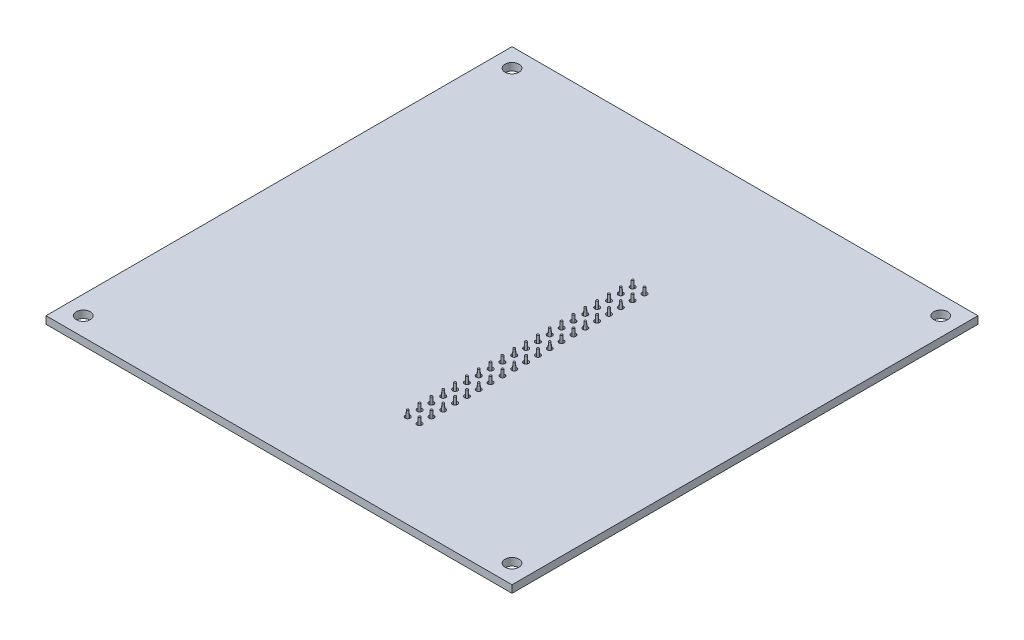
SolidWorks part; units mm, degrees
ref_plane "Front Plane" through (0, 0, 0) normal (0, 0, 1) x (1, 0, 0)
ref_plane "Top Plane" through (0, 0, 0) normal (0, 1, 0) x (1, 0, 0)
ref_plane "Right Plane" through (0, 0, 0) normal (1, 0, 0) x (0, 0, -1)
sketch "Sketch1" plane through (0, 0, 0) normal (0, 1, 0) x (1, 0, 0)
  line L1 (-50, -50) -> (50, -50)
  line L2 (-50, -50) -> (-50, 50)
  line L3 (-50, 50) -> (50, 50)
  line L4 (50, -50) -> (50, 50)
  line L5 (-50, -50) -> (50, 50) construction
  line L6 (-50, 50) -> (50, -50) construction
  point P0 (0, 0)
  dimension "D1" = 100
  dimension "D2" = 100
extrude "Boss-Extrude1" add sketch "Sketch1" along normal blind 1.6
sketch "Sketch2" plane through (0, 1.6, 0) normal (0, 1, 0) x (1, 0, 0)
  line L0 (10.138, -29.974) -> (10.138, -27.434) construction
  circle A0 centre (10.138, -29.974) radius 0.535
  circle A1 centre (7.598, -29.974) radius 0.535
  circle A2 centre (7.598, -27.434) radius 0.535
  circle A3 centre (7.598, -24.894) radius 0.535
  circle A4 centre (7.598, -22.354) radius 0.535
  circle A5 centre (7.598, -19.814) radius 0.535
  circle A6 centre (7.598, -17.274) radius 0.535
  circle A7 centre (7.598, -14.734) radius 0.535
  circle A8 centre (7.598, -12.194) radius 0.535
  circle A9 centre (7.598, -9.654) radius 0.535
  circle A10 centre (7.598, -7.114) radius 0.535
  circle A11 centre (7.598, -4.574) radius 0.535
  circle A12 centre (7.598, -2.034) radius 0.535
  circle A13 centre (7.598, 0.506) radius 0.535
  circle A14 centre (7.598, 3.046) radius 0.535
  circle A15 centre (7.598, 5.586) radius 0.535
  circle A16 centre (7.598, 8.126) radius 0.535
  circle A17 centre (7.598, 10.666) radius 0.535
  circle A18 centre (7.598, 13.206) radius 0.535
  circle A19 centre (7.598, 15.746) radius 0.535
  circle A20 centre (7.598, 18.286) radius 0.535
  circle A21 centre (10.138, -27.434) radius 0.535
  circle A22 centre (10.138, -24.894) radius 0.535
  circle A23 centre (10.138, -22.354) radius 0.535
  circle A24 centre (10.138, -19.814) radius 0.535
  circle A25 centre (10.138, -17.274) radius 0.535
  circle A26 centre (10.138, -14.734) radius 0.535
  circle A27 centre (10.138, -12.194) radius 0.535
  circle A28 centre (10.138, -9.654) radius 0.535
  circle A29 centre (10.138, -7.114) radius 0.535
  circle A30 centre (10.138, -4.574) radius 0.535
  circle A31 centre (10.138, -2.034) radius 0.535
  circle A32 centre (10.138, 0.506) radius 0.535
  circle A33 centre (10.138, 3.046) radius 0.535
  circle A34 centre (10.138, 5.586) radius 0.535
  circle A35 centre (10.138, 8.126) radius 0.535
  circle A36 centre (10.138, 10.666) radius 0.535
  circle A37 centre (10.138, 13.206) radius 0.535
  circle A38 centre (10.138, 15.746) radius 0.535
  circle A39 centre (10.138, 18.286) radius 0.535
  dimension "D1" = 1.07
  dimension "D2" = 39.862
  dimension "D3" = 20.026
  dimension "D6" = 2.54
  dimension "D4" = 2
  dimension "D5" = 20
extrude "Cut-Extrude1" cut sketch "Sketch2" against normal through all
ref_plane "Plane1" through (0, -9.4, 0) normal (0, -1, 0) x (-1, 0, 0)
sketch "Sketch4" plane through (0, -9.4, 0) normal (0, 1, 0) x (1, 0, 0)
  line L0 (9.368, -29.204) -> (10.908, -29.204)
  line L1 (8.868, -31.244) -> (11.408, -31.244)
  line L2 (8.868, -31.244) -> (8.868, -28.704)
  line L3 (8.868, -28.704) -> (11.408, -28.704)
  line L4 (11.408, -31.244) -> (11.408, -28.704)
  line L5 (8.868, -31.244) -> (11.408, -28.704) construction
  line L6 (8.868, -28.704) -> (11.408, -31.244) construction
  line L7 (10.908, -30.744) -> (10.908, -29.204)
  line L8 (9.368, -30.744) -> (10.908, -30.744)
  line L9 (9.368, -30.744) -> (9.368, -29.204)
  point P0 (10.138, -29.974)
  dimension "D1" = 2.54
  dimension "D2" = 2.54
  dimension "D3" = 0.5
extrude "Boss-Extrude2" add sketch "Sketch4" against normal blind 8.4
pattern_linear "LPattern2" count 20 spacing 2.54 along (0, 0, -1) count 2 spacing 2.54 along (-1, 0, 0) of "Boss-Extrude2"
sketch "Sketch5" plane through (0, -9.4, 0) normal (0, -1, 0) x (-1, 0, 0)
  circle A0 centre (-7.598, 3.046) radius 0.535 construction
  circle A1 centre (-7.598, 5.586) radius 0.535 construction
  circle A2 centre (-7.598, 8.126) radius 0.535 construction
  circle A3 centre (-7.598, 10.666) radius 0.535 construction
  circle A4 centre (-7.598, 13.206) radius 0.535 construction
  circle A5 centre (-7.598, 15.746) radius 0.535 construction
  circle A6 centre (-7.598, 18.286) radius 0.535 construction
  circle A7 centre (-10.138, 18.286) radius 0.535 construction
  circle A8 centre (-10.138, 15.746) radius 0.535 construction
  circle A9 centre (-10.138, 13.206) radius 0.535 construction
  circle A10 centre (-10.138, 10.666) radius 0.535 construction
  circle A11 centre (-10.138, 8.126) radius 0.535 construction
  circle A12 centre (-10.138, 5.586) radius 0.535 construction
  circle A13 centre (-10.138, 3.046) radius 0.535 construction
  circle A14 centre (-7.598, 0.506) radius 0.535 construction
  circle A15 centre (-10.138, 0.506) radius 0.535 construction
  circle A16 centre (-10.138, -2.034) radius 0.535 construction
  circle A17 centre (-7.598, -2.034) radius 0.535 construction
  circle A18 centre (-7.598, -4.574) radius 0.535 construction
  circle A19 centre (-10.138, -4.574) radius 0.535 construction
  circle A20 centre (-10.138, -7.114) radius 0.535 construction
  circle A21 centre (-7.598, -7.114) radius 0.535 construction
  circle A22 centre (-7.598, -9.654) radius 0.535 construction
  circle A23 centre (-10.138, -9.654) radius 0.535 construction
  circle A24 centre (-7.598, -12.194) radius 0.535 construction
  circle A25 centre (-10.138, -12.194) radius 0.535 construction
  circle A26 centre (-10.138, -14.734) radius 0.535 construction
  circle A27 centre (-7.598, -14.734) radius 0.535 construction
  circle A28 centre (-7.598, -17.274) radius 0.535 construction
  circle A29 centre (-10.138, -17.274) radius 0.535 construction
  circle A30 centre (-10.138, -19.814) radius 0.535 construction
  circle A31 centre (-7.598, -19.814) radius 0.535 construction
  circle A32 centre (-7.598, -22.354) radius 0.535 construction
  circle A33 centre (-10.138, -22.354) radius 0.535 construction
  circle A34 centre (-7.598, -24.894) radius 0.535 construction
  circle A35 centre (-10.138, -24.894) radius 0.535 construction
  circle A36 centre (-7.598, -27.434) radius 0.535 construction
  circle A37 centre (-10.138, -27.434) radius 0.535 construction
  circle A38 centre (-10.138, -29.974) radius 0.535 construction
  circle A39 centre (-7.598, -29.974) radius 0.535 construction
  circle A40 centre (-7.598, 3.046) radius 0.535
  circle A41 centre (-7.598, 5.586) radius 0.535
  circle A42 centre (-7.598, 8.126) radius 0.535
  circle A43 centre (-7.598, 10.666) radius 0.535
  circle A44 centre (-7.598, 13.206) radius 0.535
  circle A45 centre (-7.598, 15.746) radius 0.535
  circle A46 centre (-7.598, 18.286) radius 0.535
  circle A47 centre (-10.138, 18.286) radius 0.535
  circle A48 centre (-10.138, 15.746) radius 0.535
  circle A49 centre (-10.138, 13.206) radius 0.535
  circle A50 centre (-10.138, 10.666) radius 0.535
  circle A51 centre (-10.138, 8.126) radius 0.535
  circle A52 centre (-10.138, 5.586) radius 0.535
  circle A53 centre (-10.138, 3.046) radius 0.535
  circle A54 centre (-7.598, 0.506) radius 0.535
  circle A55 centre (-10.138, 0.506) radius 0.535
  circle A56 centre (-10.138, -2.034) radius 0.535
  circle A57 centre (-7.598, -2.034) radius 0.535
  circle A58 centre (-7.598, -4.574) radius 0.535
  circle A59 centre (-10.138, -4.574) radius 0.535
  circle A60 centre (-10.138, -7.114) radius 0.535
  circle A61 centre (-7.598, -7.114) radius 0.535
  circle A62 centre (-7.598, -9.654) radius 0.535
  circle A63 centre (-10.138, -9.654) radius 0.535
  circle A64 centre (-7.598, -12.194) radius 0.535
  circle A65 centre (-10.138, -12.194) radius 0.535
  circle A66 centre (-10.138, -14.734) radius 0.535
  circle A67 centre (-7.598, -14.734) radius 0.535
  circle A68 centre (-7.598, -17.274) radius 0.535
  circle A69 centre (-10.138, -17.274) radius 0.535
  circle A70 centre (-10.138, -19.814) radius 0.535
  circle A71 centre (-7.598, -19.814) radius 0.535
  circle A72 centre (-7.598, -22.354) radius 0.535
  circle A73 centre (-10.138, -22.354) radius 0.535
  circle A74 centre (-7.598, -24.894) radius 0.535
  circle A75 centre (-10.138, -24.894) radius 0.535
  circle A76 centre (-7.598, -27.434) radius 0.535
  circle A77 centre (-10.138, -27.434) radius 0.535
  circle A78 centre (-10.138, -29.974) radius 0.535
  circle A79 centre (-7.598, -29.974) radius 0.535
extrude "Boss-Extrude3" add sketch "Sketch5" against normal blind 12.3 draft 1.5 separate body
sketch "Sketch6" plane through (0, 1.6, 0) normal (0, 1, 0) x (1, 0, 0)
  line L0 (-50, 50) -> (-50, -50) construction
  line L1 (50, 50) -> (-50, 50) construction
  line L2 (0, 0) -> (0, 50000) construction
  line L3 (0, 0) -> (-50000, 0) construction
  circle A0 centre (-46, 46) radius 1.5
  circle A1 centre (-46, -46) radius 1.5
  circle A2 centre (46, -46) radius 1.5
  circle A3 centre (46, 46) radius 1.5
  dimension "D1" = 3
  dimension "D2" = 4
  dimension "D3" = 4
extrude "Cut-Extrude2" cut sketch "Sketch6" against normal through all both and the other way through all
